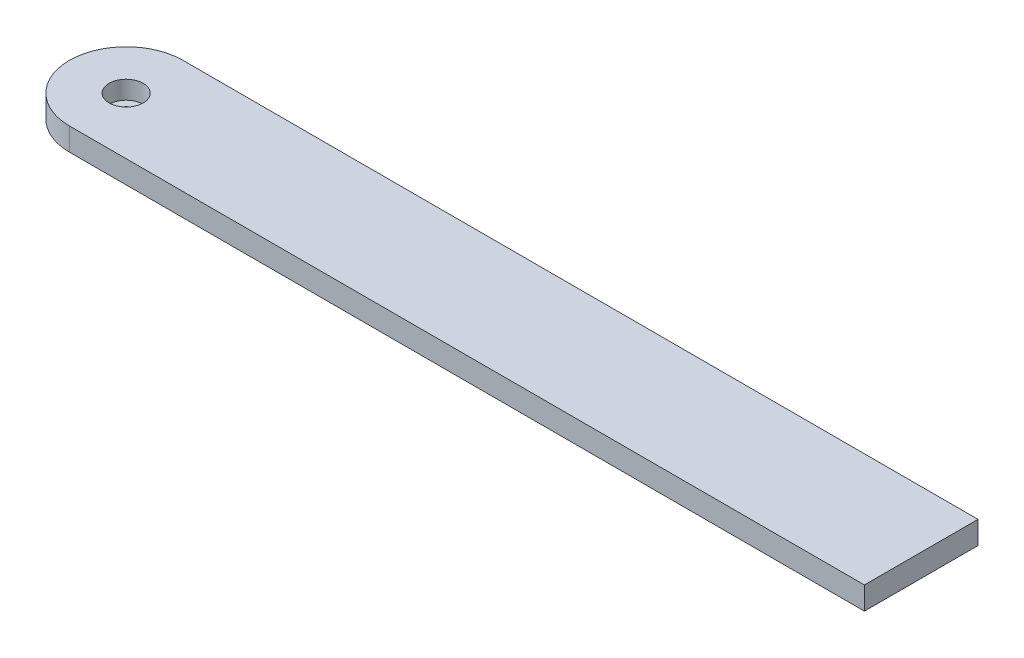
SolidWorks part; units mm, degrees
ref_plane "Front Plane" through (0, 0, 0) normal (0, 0, 1) x (1, 0, 0)
ref_plane "Top Plane" through (0, 0, 0) normal (0, 1, 0) x (1, 0, 0)
ref_plane "Right Plane" through (0, 0, 0) normal (1, 0, 0) x (0, 0, -1)
sketch "Sketch1" plane through (0, 0, 0) normal (0, 1, 0) x (1, 0, 0)
  line L1 (0, -5) -> (70, -5)
  line L2 (0, -5) -> (0, 5)
  line L3 (0, 5) -> (70, 5)
  line L4 (70, -5) -> (70, 5)
  circle A0 centre (0, 0) radius 5
  dimension "D1" = 10
  dimension "D2" = 70
extrude "Boss-Extrude1" add sketch "Sketch1" along normal blind 2 contours A0 L1 L4 L3 | L2 A0 | L2 A0 region at (36.9541, 0, 0) region at (-2.1221, 0, 0) region at (2.1221, 0, 0)
sketch "Sketch2" plane through (0, 2, 0) normal (0, 1, 0) x (1, 0, 0)
  circle A0 centre (0, 0) radius 1.5
extrude "Cut-Extrude1" cut sketch "Sketch2" against normal blind 1.6
sketch "Sketch3" plane through (0, 0.4, 0) normal (0, 1, 0) x (1, 0, 0)
  circle A0 centre (0, 0) radius 0.8
extrude "Cut-Extrude2" cut sketch "Sketch3" against normal blind 3
